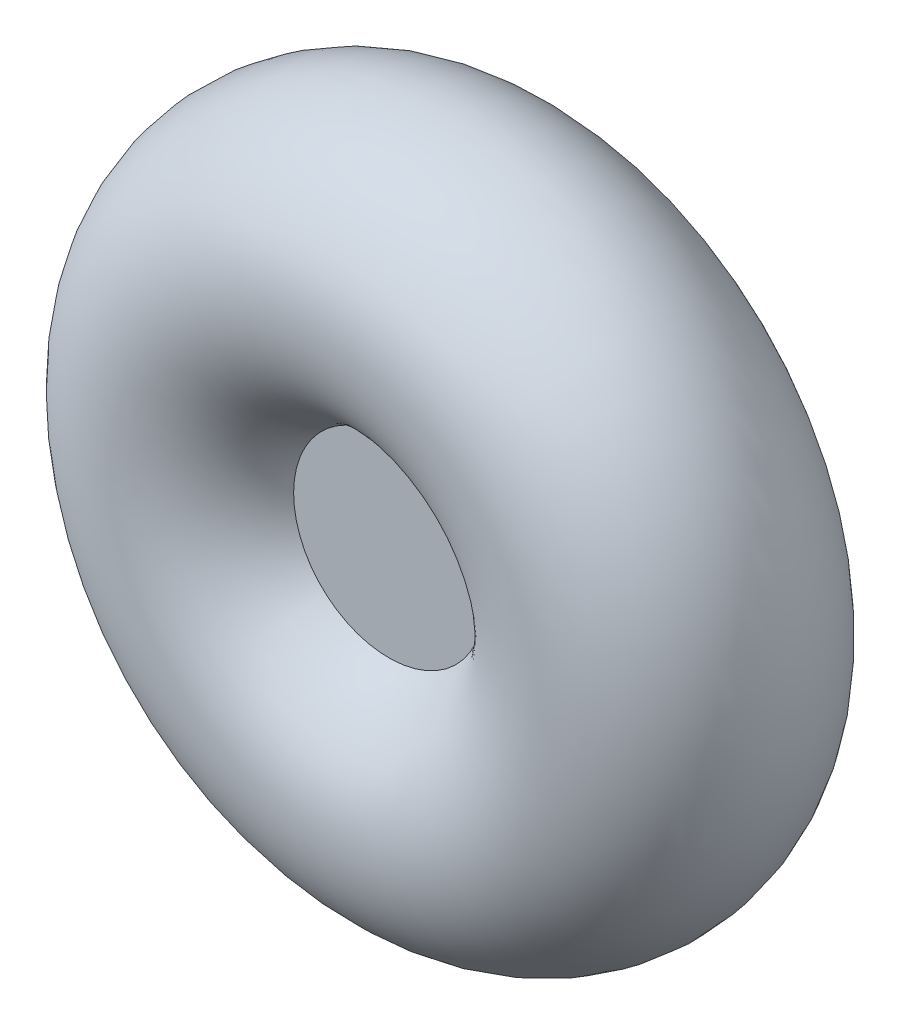
SolidWorks part; units mm, degrees
ref_plane "Front Plane" through (0, 0, 0) normal (0, 0, 1) x (1, 0, 0)
ref_plane "Top Plane" through (0, 0, 0) normal (0, 1, 0) x (1, 0, 0)
ref_plane "Right Plane" through (0, 0, 0) normal (1, 0, 0) x (0, 0, -1)
sketch "Sketch1" plane through (0, 0, 0) normal (1, 0, 0) x (0, 0, -1)
  line L0 (0, 0) -> (0, 53.975) construction
  line L1 (0, 0) -> (-19.0058, 0) construction
  line L2 (0, 0) -> (17.8325, 0) construction
  line L4 (-9.5029, 0) -> (9.5029, 0)
  line L5 (-9.5029, 0) -> (-9.5029, 14.746)
  line L6 (-9.5029, 14.746) -> (9.5029, 14.746)
  line L7 (9.5029, 0) -> (9.5029, 14.746)
  circle A0 centre (0, 33.2095) radius 20.7655
  point P11 (0, 0)
  dimension "D3" = 41.531
  dimension "D1" = 53.975
  dimension "D2" = 19.0058
revolve "Revolve1" add sketch "Sketch1" angle 360 about L1 region at (0, 6.6143, 0) region at (0, 33.6412, 0) region at (0, 13.8207, 0)
